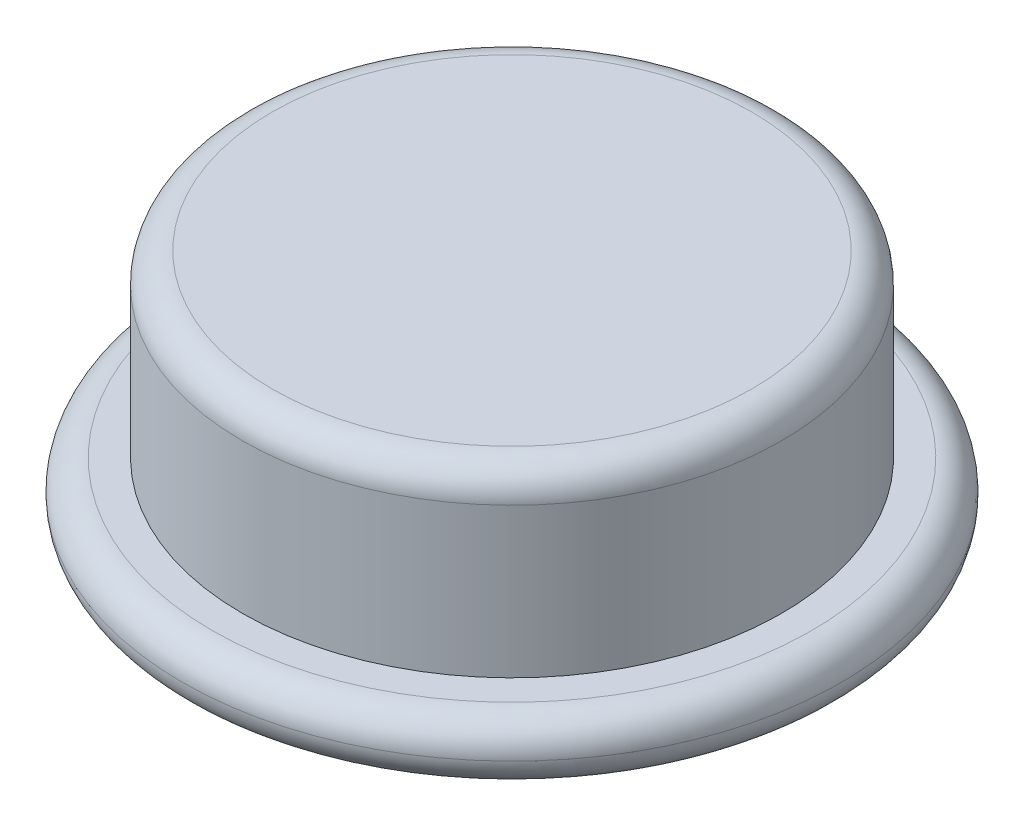
SolidWorks part; units mm, degrees
ref_plane "Front Plane" through (0, 0, 0) normal (0, 0, 1) x (1, 0, 0)
ref_plane "Top Plane" through (0, 0, 0) normal (0, 1, 0) x (1, 0, 0)
ref_plane "Right Plane" through (0, 0, 0) normal (1, 0, 0) x (0, 0, -1)
sketch "Sketch1" plane through (0, 0, 0) normal (1, 0, 0) x (0, 0, -1)
  line L0 (0, 0) -> (0, 4)
  line L1 (0, 4) -> (-4.5125, 4)
  line L2 (-4.5125, 4) -> (-4.5125, 1)
  line L3 (-4.5125, 1) -> (-5.5125, 1)
  line L4 (-5.5125, 1) -> (-5.5125, 0)
  line L5 (-5.5125, 0) -> (0, 0)
  line L6 (0, 0) -> (0, -2.0116) construction
  dimension "D1" = 9.025
  dimension "D2" = 3
  dimension "1mm" = 1
  dimension "4" = 4
revolve "Revolve1" add sketch "Sketch1" angle 360 about L6
fillet "Fillet1" radius 0.5 3 edges at (0, 0, 5.5125) (0, 1, 5.5125) (0, 4, 4.5125)
